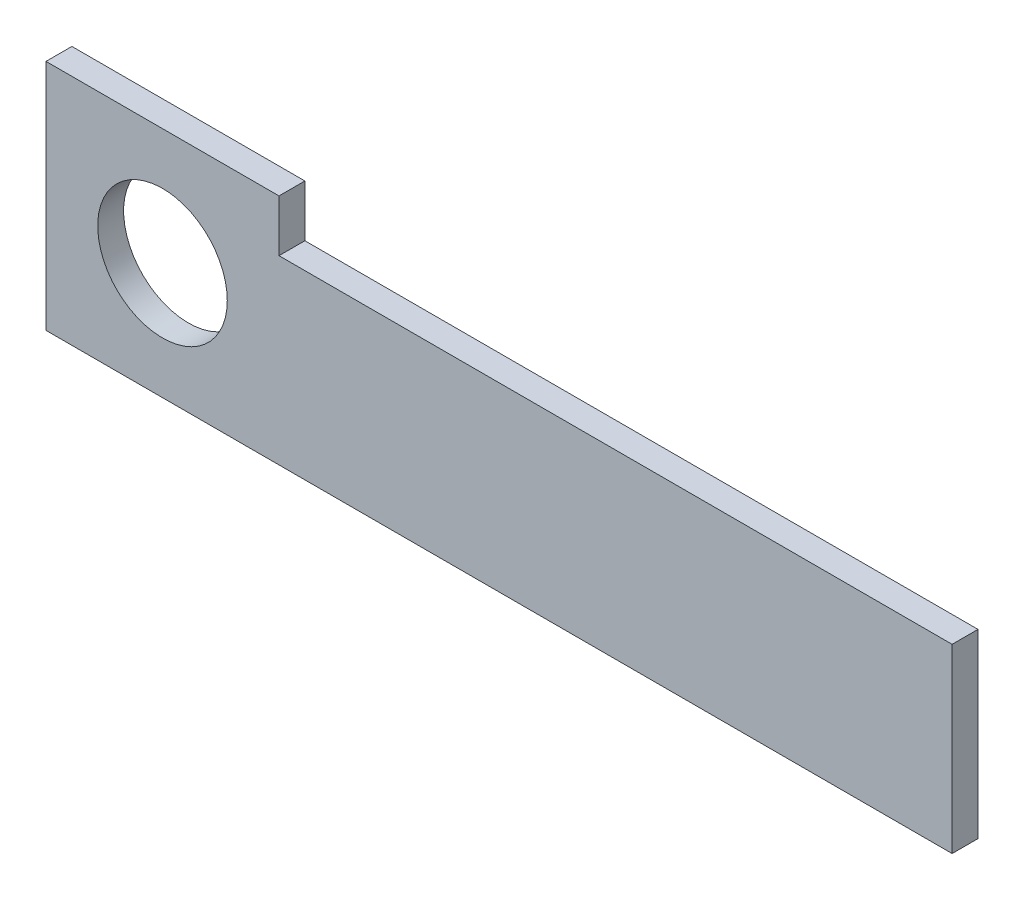
SolidWorks part; units mm, degrees
material "Plain Carbon Steel"
ref_plane "Front Plane" through (0, 0, 0) normal (0, 0, 1) x (1, 0, 0)
ref_plane "Top Plane" through (0, 0, 0) normal (0, 1, 0) x (1, 0, 0)
ref_plane "Right Plane" through (0, 0, 0) normal (1, 0, 0) x (0, 0, -1)
sketch "Sketch1" plane through (0, 0, 0) normal (0, 0, 1) x (1, 0, 0)
  line L0 (26.6994, -267.07) -> (-10.3006, -267.07) construction
  line L1 (-20.3006, -267.07) -> (-280.3006, -267.07)
  line L2 (-20.3006, -267.07) -> (-20.3006, -337.07)
  line L3 (-20.3006, -337.07) -> (-370.3006, -337.07)
  line L4 (-370.3006, -267.07) -> (-370.3006, -337.07)
  line L5 (-267.3006, -337.07) -> (26.6994, -337.07) construction
  line L6 (-20.3006, -282.07) -> (-20.3006, -330.07) construction
  line L8 (-280.3006, -267.07) -> (-280.3006, -247.07)
  line L9 (-280.3006, -247.07) -> (-370.3006, -247.07)
  line L10 (-370.3006, -247.07) -> (-370.3006, -267.07)
  line L11 (-270.3006, -282.07) -> (-270.3006, -330.07) construction
  line L12 (-280.3006, -247.07) -> (-280.3006, -337.07) construction
  line L13 (-370.3006, -292.07) -> (-280.3006, -292.07) construction
  line L14 (-325.3006, -247.07) -> (-325.3006, -337.07) construction
  line L15 (-325.3006, -292.07) -> (-357.1204, -260.2502) construction
  line L16 (-325.3006, -292.07) -> (-293.4808, -260.2502) construction
  line L17 (-325.3006, -292.07) -> (-293.4808, -323.8898) construction
  line L18 (-325.3006, -292.07) -> (-357.1204, -323.8898) construction
  circle A0 centre (-325.3006, -292.07) radius 45 construction
  point P15 (-280.3006, -292.07)
  point P21 (-325.3006, -292.07)
  point P23 (-325.3006, -292.07)
  point P32 (-325.3006, -292.07)
  dimension "D1" = 90
  dimension "D2" = 10
  dimension "D3" = 90
  dimension "D5" = 45
  dimension "D6" = 4
extrude "Boss-Extrude1" add sketch "Sketch1" along normal blind 10
sketch "Sketch2" plane through (0, 0, 10) normal (0, 0, 1) x (1, 0, 0)
  circle A0 centre (-325.3006, -292.07) radius 25.025
  dimension "D1" = 50.05
extrude "Cut-Extrude1" cut sketch "Sketch2" against normal through all
